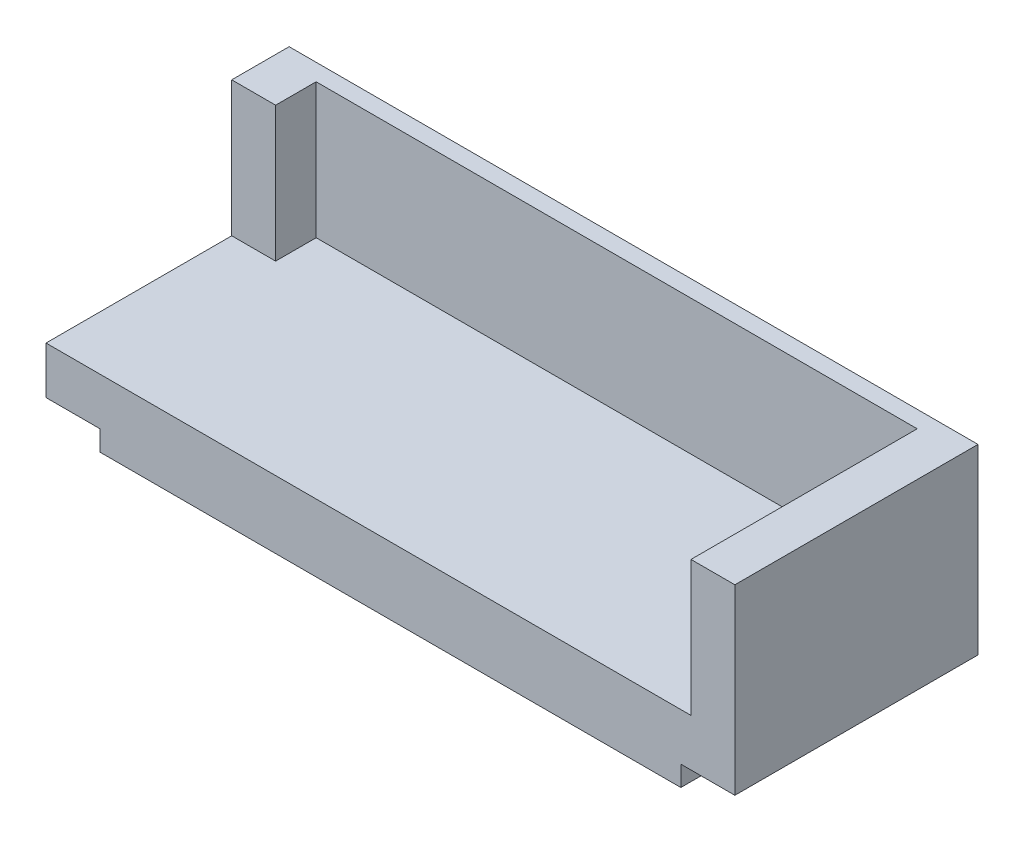
SolidWorks part; units mm, degrees
ref_plane "Plan de face" through (0, 0, 0) normal (0, 0, 1) x (1, 0, 0)
ref_plane "Plan de dessus" through (0, 0, 0) normal (0, 1, 0) x (1, 0, 0)
ref_plane "Plan de droite" through (0, 0, 0) normal (1, 0, 0) x (0, 0, -1)
sketch "Esquisse2" plane through (0, 0, 0) normal (0, 1, 0) x (1, 0, 0)
  line L1 (43, 18) -> (0, 18)
  line L2 (43, 18) -> (43, 0)
  line L3 (43, 0) -> (0, 0)
  line L4 (0, 18) -> (0, 0)
  point P13 (0, 0)
  point P15 (0, 0)
  dimension "D1" = 43
  dimension "D2" = 18
extrude "Boss.-Extru.1" add sketch "Esquisse2" along normal blind 3.5 and the other way blind 1.5
sketch "Esquisse3" plane through (43, 0, 0) normal (1, 0, 0) x (0, 0, -1)
  line L1 (0, 0) -> (18, 0)
  line L2 (0, 0) -> (0, 3.5)
  line L3 (0, 3.5) -> (18, 3.5)
  line L4 (18, 0) -> (18, 3.5)
sketch "Esquisse4" plane through (0, 0, 0) normal (-1, 0, 0) x (0, 0, 1)
  line L1 (0, 0) -> (-18, 0)
  line L2 (0, 0) -> (0, 3.5)
  line L3 (0, 3.5) -> (-18, 3.5)
  line L4 (-18, 0) -> (-18, 3.5)
extrude "Boss.-Extru.2" add sketch "Esquisse3" along normal blind 4
extrude "Boss.-Extru.3" add sketch "Esquisse4" along normal blind 4
sketch "Esquisse5" plane through (0, 3.5, 0) normal (0, 1, 0) x (1, 0, 0)
  line L0 (-4, 16.75) -> (47, 16.75) construction
  line L1 (-4, 0) -> (-4, 18) construction
  line L2 (47, 18) -> (47, 0) construction
  line L3 (47, 18) -> (-4, 18) construction
  line L5 (-4, 18) -> (47, 18)
  line L6 (-4, 18) -> (-4, 16.75)
  line L7 (-4, 16.75) -> (47, 16.75)
  line L8 (47, 18) -> (47, 16.75)
  dimension "D1" = 1.25
extrude "Boss.-Extru.4" add sketch "Esquisse5" along normal blind 10
sketch "Esquisse6" plane through (0, 3.5, 0) normal (0, 1, 0) x (1, 0, 0)
  line L0 (-4, 0) -> (47, 0) construction
  line L1 (47, 16.75) -> (43.75, 16.75)
  line L2 (47, 16.75) -> (47, 0)
  line L3 (47, 0) -> (43.75, 0)
  line L4 (43.75, 16.75) -> (43.75, 0)
  dimension "D1" = 3.25
extrude "Boss.-Extru.5" add sketch "Esquisse6" along normal blind 10
sketch "Esquisse7" plane through (0, 3.5, 0) normal (0, 1, 0) x (1, 0, 0)
  line L1 (-4, 16.75) -> (-0.75, 16.75)
  line L2 (-4, 16.75) -> (-4, 13.75)
  line L3 (-4, 13.75) -> (-0.75, 13.75)
  line L4 (-0.75, 16.75) -> (-0.75, 13.75)
  dimension "D1" = 3
  dimension "D2" = 3.25
extrude "Boss.-Extru.6" add sketch "Esquisse7" along normal blind 10
